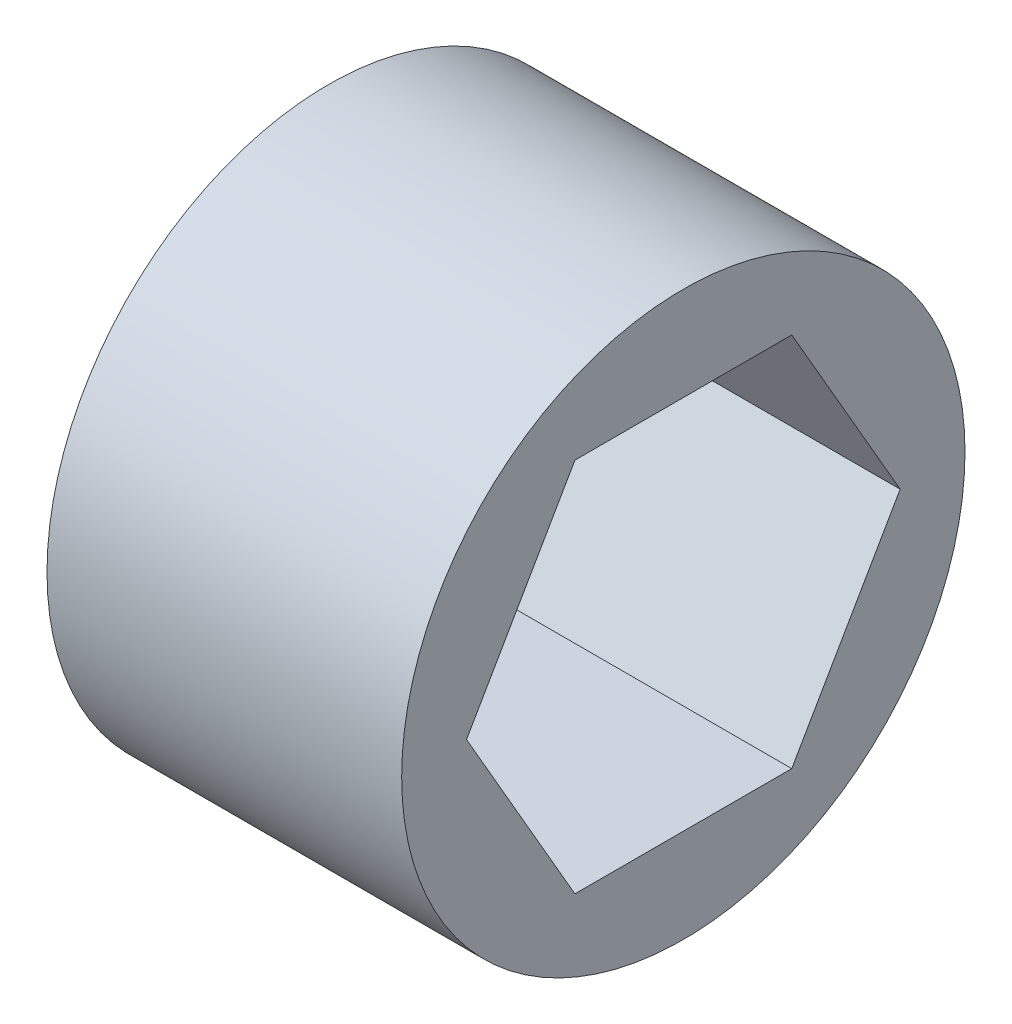
SolidWorks part; units mm, degrees
material "PET"
ref_plane "Front" through (0, 0, 0) normal (0, 0, 1) x (1, 0, 0)
ref_plane "Top" through (0, 0, 0) normal (0, 1, 0) x (1, 0, 0)
ref_plane "Right" through (0, 0, 0) normal (1, 0, 0) x (0, 0, -1)
sketch "Sketch1" plane through (0, 0, 0) normal (1, 0, 0) x (0, 0, -1)
  line L1 (7.3323, 0) -> (3.6662, 6.35)
  line L2 (3.6662, 6.35) -> (-3.6662, 6.35)
  line L3 (-3.6662, 6.35) -> (-7.3323, 0)
  line L4 (-7.3323, 0) -> (-3.6662, -6.35)
  line L5 (-3.6662, -6.35) -> (3.6662, -6.35)
  line L6 (3.6662, -6.35) -> (7.3323, 0)
  circle A0 centre (0, 0) radius 6.35 construction
  circle A1 centre (0, 0) radius 9.525
  dimension "D2" = 19.05
  dimension "D1" = 12.7
extrude "Boss-Extrude1" add sketch "Sketch1" along normal blind 11.994
